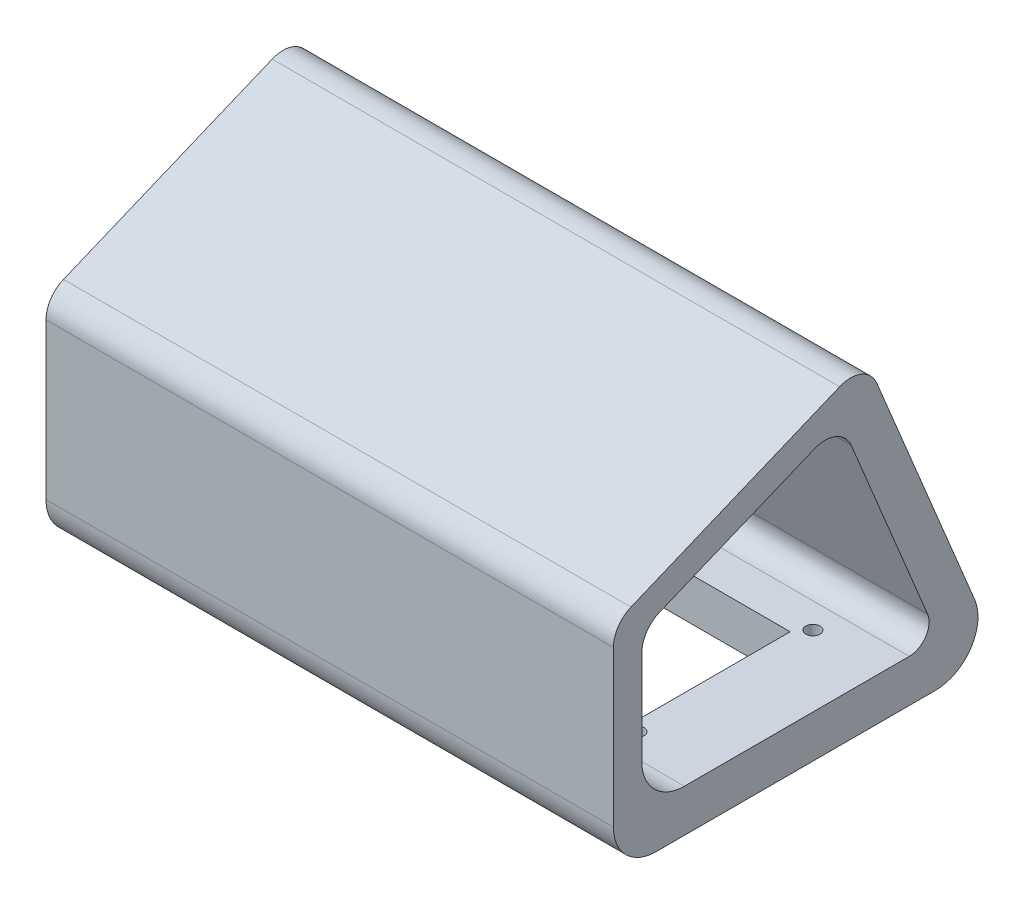
SolidWorks part; units mm, degrees
ref_plane "Front Plane" through (0, 0, 0) normal (0, 0, 1) x (1, 0, 0)
ref_plane "Top Plane" through (0, 0, 0) normal (0, 1, 0) x (1, 0, 0)
ref_plane "Right Plane" through (0, 0, 0) normal (1, 0, 0) x (0, 0, -1)
sketch "Sketch1" plane through (0, 0, 0) normal (0, 1, 0) x (1, 0, 0)
  line L0 (-50, 0) -> (50, 0) construction
  line L1 (-50, 32.7175) -> (50, 32.7175)
  line L2 (-50, 32.7175) -> (-50, -32.7175)
  line L3 (-50, -32.7175) -> (50, -32.7175)
  line L4 (50, 32.7175) -> (50, -32.7175)
  line L5 (-50, 32.7175) -> (50, -32.7175) construction
  line L6 (-50, -32.7175) -> (50, 32.7175) construction
  line L7 (0, 32.7175) -> (0, -32.7175) construction
  line L9 (-35.75, 13.25) -> (35.75, 13.25)
  line L10 (-35.75, 13.25) -> (-35.75, -13.25)
  line L11 (-35.75, -13.25) -> (35.75, -13.25)
  line L12 (35.75, 13.25) -> (35.75, -13.25)
  line L13 (-35.75, 13.25) -> (35.75, -13.25) construction
  line L14 (-35.75, -13.25) -> (35.75, 13.25) construction
  circle A0 centre (-37.5, 15.5) radius 1.25
  point P0 (0, 0)
  point P10 (0, 0)
  dimension "D3" = 2.5
  dimension "D1" = 26.5
  dimension "D2" = 71.5
  dimension "D4" = 15.5
  dimension "D5" = 37.5
  dimension "D6" = 100
extrude "Boss-Extrude1" add sketch "Sketch1" along normal blind 7.5
ref_plane "Plane1" through (0, 0, 0) normal (-1, 0, 0) x (0, 0, 1)
ref_plane "Plane2" through (0, 0, 0) normal (0, 0, -1) x (-1, 0, 0)
mirror "Mirror2" about plane through (0, 0, 0) normal (-1, 0, 0) of face at (-37.5, 7.5, -14.25)
mirror "Mirror3" about plane through (0, 0, 0) normal (0, 0, -1) of face at (37.5, 7.5, -14.25) of face at (-37.5, 7.5, -14.25)
sketch "Sketch4" plane through (50, 0, 0) normal (1, 0, 0) x (0, 0, -1)
  line L0 (28.3241, 0) -> (8.6492, 47.4995)
  line L1 (-32.7175, 0) -> (32.7175, 0) construction
  line L2 (32.7175, 7.5) -> (16.1492, 47.4995)
  line L3 (16.1492, 47.4995) -> (8.6492, 47.4995)
  line L4 (-32.7175, 7.5) -> (32.7175, 7.5) construction
  line L7 (32.7175, 7.5) -> (35.8241, 0)
  line L8 (35.8241, 0) -> (28.3241, 0)
  dimension "D1" = 7.5
  dimension "D2" = 67.5
extrude "Boss-Extrude2" add sketch "Sketch4" against normal up to surface (100 mm away) up to face at (-50, 3.75, 0)
fillet "Fillet2" radius 7.5 1 edges at (0, 0, -35.8241)
sketch "Sketch5" plane through (50, 0, 0) normal (1, 0, 0) x (0, 0, -1)
  line L0 (-32.7175, 7.5) -> (25.2175, 7.5) construction
  line L1 (-34.646, -3.3641) -> (-27.146, -3.3641)
  line L2 (-34.646, -3.3641) -> (-34.646, 7.5)
  line L3 (-34.646, 7.5) -> (-27.146, 7.5)
  line L4 (-27.146, -3.3641) -> (-27.146, 7.5)
  dimension "D1" = 7.5
extrude "Cut-Extrude2" cut sketch "Sketch5" against normal through all both and the other way through all
sketch "Sketch6" plane through (50, 0, 0) normal (1, 0, 0) x (0, 0, -1)
  line L0 (-27.146, 0) -> (-32.146, 0)
  line L1 (-32.146, 0) -> (-32.146, 38.2749)
  line L2 (-27.146, 0) -> (-27.146, 34.934)
  line L3 (-27.146, 34.934) -> (7.8497, 49.4297)
  line L4 (16.1492, 47.4995) -> (13.4853, 53.9307)
  line L5 (31.5287, 10.3701) -> (16.1492, 47.4995) construction
  line L6 (-32.146, 38.2749) -> (12.3379, 56.7007)
  line L7 (12.3379, 56.7007) -> (13.4853, 53.9307)
  line L8 (16.1492, 47.4995) -> (12.9391, 38.2749)
  line L9 (12.9391, 38.2749) -> (8.6649, 47.4614)
  line L10 (8.6492, 47.4995) -> (25.2175, 7.5) construction
  line L11 (8.6649, 47.4614) -> (7.8497, 49.4297)
  dimension "D1" = 5
  dimension "D2" = 5
extrude "Boss-Extrude3" add sketch "Sketch6" against normal up to surface (100 mm away) up to face at (-50, 16.931, -7.8034)
fillet "Fillet4" radius 3.5 1 edges at (0, 7.5, -25.2175)
fillet "Fillet5" radius 7.5 2 edges at (0, 0, 32.146) (0, 7.5, 27.146)
fillet "Fillet6" radius 5 4 edges at (0, 49.4297, -7.8497) (0, 56.7007, -12.3379) (0, 34.934, 27.146) (0, 38.2749, 32.146)
fillet "Fillet7" [suppressed] radius 5
sketch "Sketch7" plane through (-50, 0, 0) normal (-1, 0, 0) x (0, 0, 1)
  line L0 (-23.213, 12.3394) -> (-9.7631, 44.8103) construction
  line L1 (-19.9794, 7.5) -> (19.646, 7.5) construction
  line L2 (27.146, 31.5931) -> (27.146, 15) construction
  line L3 (-3.2303, 47.5163) -> (24.0594, 36.2125) construction
  line L4 (29.0594, 39.5534) -> (-7.7185, 54.7873)
  line L5 (-14.2513, 52.0814) -> (-31.5287, 10.3701)
  line L6 (-24.5996, 0) -> (24.646, 0)
  line L7 (32.146, 7.5) -> (32.146, 34.934)
  line L8 (29.0594, 39.5534) -> (-7.7185, 54.7873)
  line L9 (-14.2513, 52.0814) -> (-31.5287, 10.3701)
  line L10 (-24.5996, 0) -> (24.646, 0)
  line L11 (32.146, 7.5) -> (32.146, 34.934)
  line L12 (-23.213, 12.3394) -> (-9.7631, 44.8103)
  line L13 (-19.9794, 7.5) -> (19.646, 7.5)
  line L14 (27.146, 31.5931) -> (27.146, 15)
  line L15 (-3.2303, 47.5163) -> (24.0594, 36.2125)
  arc A0 (-3.2303, 47.5163) -> (-9.7631, 44.8103) centre (-5.1437, 42.8969) ccw construction
  arc A1 (-23.213, 12.3394) -> (-19.9794, 7.5) centre (-19.9794, 11) ccw construction
  arc A2 (19.646, 7.5) -> (27.146, 15) centre (19.646, 15) ccw construction
  arc A3 (27.146, 31.5931) -> (24.0594, 36.2125) centre (22.146, 31.5931) ccw construction
  arc A4 (-7.7185, 54.7873) -> (-14.2513, 52.0814) centre (-9.6319, 50.1679) ccw
  arc A5 (-31.5287, 10.3701) -> (-24.5996, 0) centre (-24.5996, 7.5) ccw
  arc A6 (24.646, 0) -> (32.146, 7.5) centre (24.646, 7.5) ccw
  arc A7 (32.146, 34.934) -> (29.0594, 39.5534) centre (27.146, 34.934) ccw
  arc A8 (-7.7185, 54.7873) -> (-14.2513, 52.0814) centre (-9.6319, 50.1679) ccw
  arc A9 (-31.5287, 10.3701) -> (-24.5996, 0) centre (-24.5996, 7.5) ccw
  arc A10 (24.646, 0) -> (32.146, 7.5) centre (24.646, 7.5) ccw
  arc A11 (32.146, 34.934) -> (29.0594, 39.5534) centre (27.146, 34.934) ccw
  arc A12 (-3.2303, 47.5163) -> (-9.7631, 44.8103) centre (-5.1437, 42.8969) ccw
  arc A13 (-23.213, 12.3394) -> (-19.9794, 7.5) centre (-19.9794, 11) ccw
  arc A14 (19.646, 7.5) -> (27.146, 15) centre (19.646, 15) ccw
  arc A15 (27.146, 31.5931) -> (24.0594, 36.2125) centre (22.146, 31.5931) ccw
  dimension "D1" = 0
